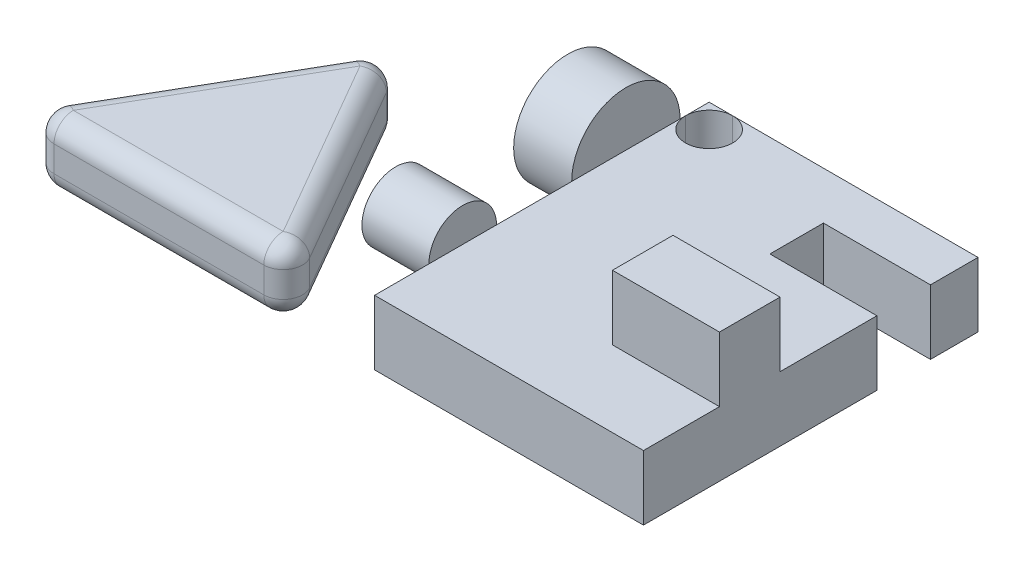
SolidWorks part; units mm, degrees
ref_plane "前视基准面" through (0, 0, 0) normal (0, 0, 1) x (1, 0, 0)
ref_plane "上视基准面" through (0, 0, 0) normal (0, 1, 0) x (1, 0, 0)
ref_plane "右视基准面" through (0, 0, 0) normal (1, 0, 0) x (0, 0, -1)
sketch "草图1" plane through (0, 0, 0) normal (0, 1, 0) x (1, 0, 0)
  line L3 (0, 0) -> (42.8602, 0)
  line L4 (42.8602, 0) -> (21.4301, 37.1181)
  line L5 (21.4301, 37.1181) -> (0, 0)
  point P2 (0, 0)
extrude "凸台-拉伸1" add sketch "草图1" along normal blind 10
fillet "圆角1" radius 3 9 edges at (21.4301, 0, 0) (32.1452, 0, -18.559) (10.7151, 0, -18.559) (32.1452, 10, -18.559) (21.4301, 10, 0) (10.7151, 10, -18.559) (0, 5, 0) (42.8602, 5, 0) (21.4301, 5, -37.1181)
sketch "草图5" plane through (0, 0, 0) normal (0, 1, 0) x (1, 0, 0)
  line L0 (53.2933, 1.516) -> (94.9045, 1.516)
  line L1 (94.9045, 1.516) -> (94.9045, 53.2865)
  line L2 (53.2933, 1.516) -> (53.2933, 53.2865)
  line L3 (53.2933, 53.2865) -> (94.9045, 53.2865)
extrude "凸台-拉伸2" add sketch "草图5" along normal blind 10 separate body
sketch "草图6" plane through (0, 10, 0) normal (0, 1, 0) x (1, 0, 0)
  line L0 (53.2933, 48.79) -> (44.3084, 48.79)
  line L1 (53.2933, 1.516) -> (53.2933, 53.2865) construction
  line L2 (44.3084, 48.79) -> (44.3084, 40.4048)
  line L3 (44.3084, 40.4048) -> (53.2933, 40.4048)
  line L4 (53.2933, 48.79) -> (53.2933, 40.4048)
revolve "旋转1" add sketch "草图6" angle 360 about L3
sketch "草图7" plane through (0, 10, 0) normal (0, 1, 0) x (1, 0, 0)
  line L0 (53.2933, 20.379) -> (42.9273, 20.379)
  line L1 (53.2933, 1.516) -> (53.2933, 32.0196) construction
  line L2 (42.9273, 20.379) -> (42.9273, 15.1506)
  line L3 (42.9273, 15.1506) -> (53.2933, 15.1506) construction
  line L4 (53.2933, 15.1506) -> (53.2933, 20.379)
  line L5 (53.2933, 15.1506) -> (42.9273, 15.1506)
revolve "旋转2" add sketch "草图7" angle 360 about L3
sketch "草图8" plane through (0, 10, 0) normal (0, 1, 0) x (1, 0, 0)
  line L0 (94.9045, 45.9292) -> (78.3424, 45.9292)
  line L5 (94.9045, 1.516) -> (94.9045, 53.2865) construction
  line L6 (78.3424, 45.9292) -> (78.3424, 37.6426)
  line L7 (78.3424, 37.6426) -> (94.9045, 37.6426)
  line L8 (94.9045, 22.6479) -> (78.3424, 22.6479)
  line L9 (78.3424, 22.6479) -> (78.3424, 13.2763)
  line L10 (78.3424, 13.2763) -> (94.9045, 13.2763)
  line L11 (94.9045, 45.9292) -> (94.9045, 37.6426)
  line L12 (94.9045, 22.6479) -> (94.9045, 13.2763)
  line M11 (94.9045, 1.516) -> (94.9045, 53.2865)
extrude "切除-拉伸1" cut sketch "草图8" against normal blind 10 contours L6 L7 L0 M11 region at (86.6235, 10, -41.7859)
extrude "凸台-拉伸3" add sketch "草图8<4>" along normal blind 10 contours L9 L10 L8 M11 region at (86.6235, 10, -17.9621)
sketch "草图8<4>" plane through (0, 10, 0) normal (0, 1, 0) x (1, 0, 0) same geometry as "草图8"
sketch "草图10" plane through (0, 10, 0) normal (0, 1, 0) x (1, 0, 0)
  line L1 (94.9045, 53.2865) -> (53.2933, 53.2865) construction
  line L2 (53.2933, 53.2865) -> (53.2933, 48.79) construction
  circle A0 centre (56.9433, 49.6365) radius 3.65
  point P2 (60.0923, 48.1981)
  point P7 (0, 0)
extrude "切除-拉伸3" cut sketch "草图10" against normal blind 10 contours A0 region at (56.9433, 10, -49.6365)
